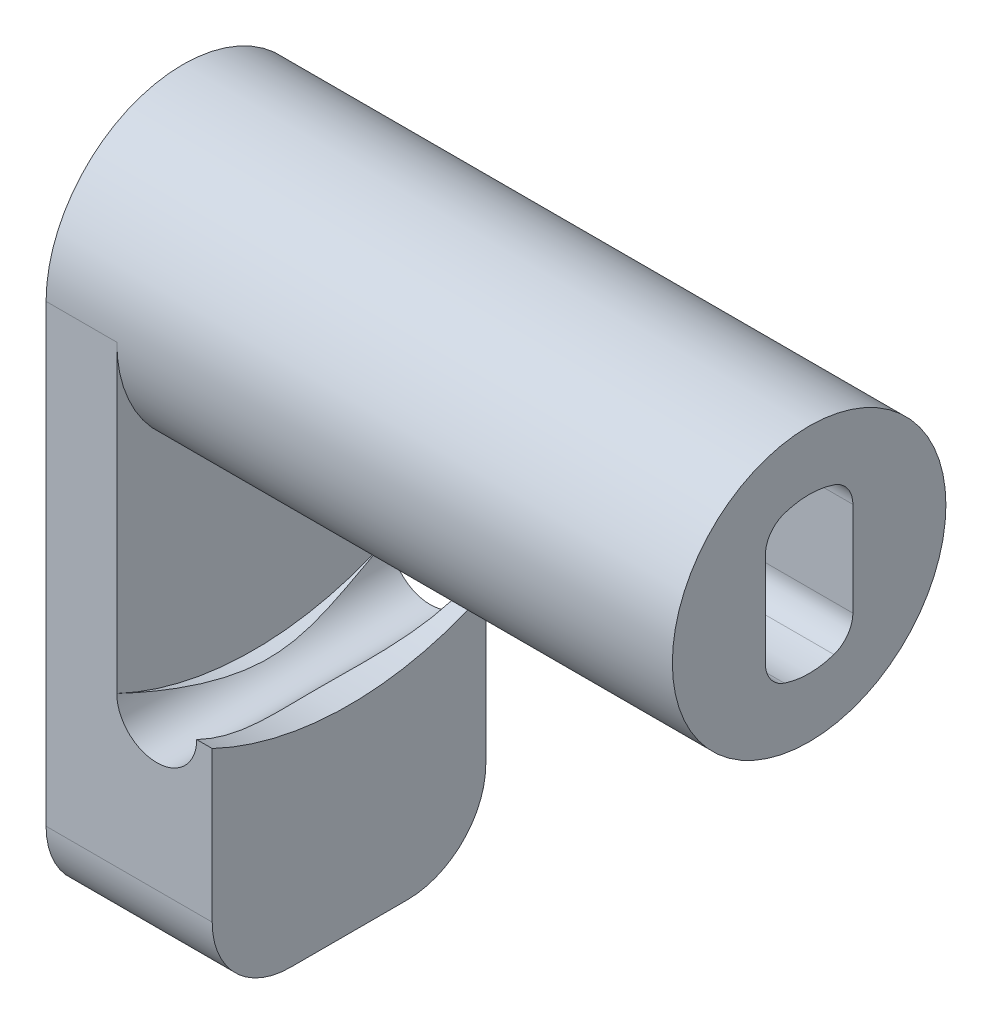
SolidWorks part; units mm, degrees
material "ABS"
ref_plane "Front Plane" through (0, 0, 0) normal (1, 0, 0) x (0, 1, 0)
ref_plane "Top Plane" through (0, 0, 0) normal (0, 0, 1) x (0, 1, 0)
ref_plane "Right Plane" through (0, 0, 0) normal (0, 1, 0) x (-1, 0, 0)
sketch "Sketch1" plane through (0, 0, 0) normal (1, 0, 0) x (0, 1, 0)
  circle A2 centre (0, 0) radius 8.7376
  dimension "D3" = 17.4752
extrude "Boss-Extrude1" add sketch "Sketch1" along normal blind 40.005 contours A2 region at (0, 0, 0)
sketch "Sketch10" plane through (0, 0, 0) normal (-1, 0, 0) x (0, -1, 0)
  line L0 (0, 8.7376) -> (34.036, 8.7376)
  line L2 (34.036, 8.7376) -> (34.036, -8.7376)
  line L3 (34.036, -8.7376) -> (0, -8.7376)
  circle A0 centre (0, 0) radius 8.7376 construction
  arc A2 (0, 8.7376) -> (0, -8.7376) centre (0, 0) cw
  dimension "D1" = 34.036
extrude "Boss-Extrude3" add sketch "Sketch10" against normal blind 4.516 contours L0 A2 L3 L2 region at (0, -20.3793, 0)
fillet "Fillet2" radius 5 2 edges at (2.258, -34.036, 8.7376) (2.258, -34.036, -8.7376)
sketch "Sketch14" [suppressed] plane through (0, 0, 0) normal (-1, 0, 0) x (0, 0, 1)
  line L0 (0.5115, -3.4237) -> (0.3944, -4.0089)
  line L1 (0, 0) -> (0, -4.064) construction
  line L2 (0, 0) -> (0.5606, -3.4335) construction
  line L3 (0.6039, -3.4087) -> (0.9011, -3.9262)
  line L4 (-0.6903, -3.3922) -> (-1.0005, -3.9021)
  line L5 (-0.5983, -3.4096) -> (-0.4961, -3.9976)
  line L6 (-1.8089, -2.9515) -> (-2.2748, -3.3245)
  line L7 (-1.7284, -2.9994) -> (-1.8334, -3.5869)
  line L8 (-2.7093, -2.1549) -> (-3.2746, -2.346)
  line L9 (-2.65, -2.2273) -> (-2.9496, -2.7435)
  line L10 (-3.2829, -1.0983) -> (-3.8795, -1.0846)
  line L11 (-3.252, -1.1867) -> (-3.7101, -1.5692)
  line L12 (-3.4605, 0.0907) -> (-4.0165, 0.3077)
  line L13 (-3.4617, -0.0029) -> (-4.023, -0.2057)
  line L14 (-3.2208, 1.2689) -> (-3.669, 1.6629)
  line L15 (-3.2539, 1.1813) -> (-3.8507, 1.1827)
  line L16 (-2.5926, 2.2939) -> (-2.879, 2.8175)
  line L17 (-2.6537, 2.223) -> (-3.214, 2.4284)
  line L18 (-1.6517, 3.0423) -> (-1.7417, 3.6323)
  line L19 (-1.7333, 2.9965) -> (-2.1896, 3.3812)
  line L20 (-0.5115, 3.4237) -> (-0.3944, 4.0089)
  line L21 (-0.6039, 3.4087) -> (-0.9011, 3.9262)
  line L22 (0.6903, 3.3922) -> (1.0005, 3.9021)
  line L23 (0.5983, 3.4096) -> (0.4961, 3.9976)
  line L24 (1.8089, 2.9515) -> (2.2748, 3.3245)
  line L25 (1.7284, 2.9994) -> (1.8334, 3.5869)
  line L26 (2.7093, 2.1549) -> (3.2746, 2.346)
  line L27 (2.65, 2.2273) -> (2.9496, 2.7435)
  line L28 (3.2829, 1.0983) -> (3.8795, 1.0846)
  line L29 (3.252, 1.1867) -> (3.7101, 1.5692)
  line L30 (3.4605, -0.0907) -> (4.0165, -0.3077)
  line L31 (3.4617, 0.0029) -> (4.023, 0.2057)
  line L32 (3.2208, -1.2689) -> (3.669, -1.6629)
  line L33 (3.2539, -1.1813) -> (3.8507, -1.1827)
  line L34 (2.5926, -2.2939) -> (2.879, -2.8175)
  line L35 (2.6537, -2.223) -> (3.214, -2.4284)
  line L36 (1.6517, -3.0423) -> (1.7417, -3.6323)
  line L37 (1.7333, -2.9965) -> (2.1896, -3.3812)
  line L38 (-0.1032, -4.0627) -> (0, -4.064)
  line L39 (-1.4865, -3.7824) -> (-1.39, -3.8189)
  line L40 (-2.6905, -3.0459) -> (-2.6123, -3.1132)
  line L41 (-3.5195, -2.032) -> (-3.57, -1.942)
  line L42 (-4.0023, -0.7057) -> (-4.0189, -0.6039)
  line L43 (-4.0023, 0.7057) -> (-3.9831, 0.8071)
  line L44 (-3.5195, 2.032) -> (-3.4668, 2.1207)
  line L45 (-2.6123, 3.1132) -> (-2.5324, 3.1785)
  line L46 (-1.39, 3.8189) -> (-1.2926, 3.853)
  line L47 (0, 4.064) -> (0.1032, 4.0627)
  line L48 (1.39, 3.8189) -> (1.4865, 3.7824)
  line L49 (2.6123, 3.1132) -> (2.6905, 3.0459)
  line L50 (3.5195, 2.032) -> (3.57, 1.942)
  line L51 (4.0023, 0.7057) -> (4.0189, 0.6039)
  line L52 (4.0023, -0.7057) -> (3.9831, -0.8071)
  line L53 (3.5195, -2.032) -> (3.4668, -2.1207)
  line L54 (2.6123, -3.1132) -> (2.5324, -3.1785)
  line L55 (1.39, -3.8189) -> (1.2926, -3.853)
  arc A0 (0.3497, -4.0489) -> (0, -4.064) centre (0, 0) cw
  arc A1 (0.3497, -4.0489) -> (0.3944, -4.0089) centre (0.3454, -3.9991) ccw
  arc A2 (0.5115, -3.4237) -> (0.6039, -3.4087) centre (0.5606, -3.4335) cw
  arc A3 (0.4203, -4.0631) -> (0.3944, -4.0089) centre (0.4434, -4.0187) cw
  arc A4 (0.4203, -4.0631) -> (0.7372, -4.2116) centre (2.3016, -0.4608) ccw
  arc A6 (0.9562, -3.9499) -> (0.9011, -3.9262) centre (0.9445, -3.9013) cw
  arc A7 (0.9562, -3.9499) -> (1.2926, -3.853) centre (0, 0) ccw
  arc A8 (-1.0562, -3.9243) -> (-1.39, -3.8189) centre (0, 0) cw
  arc A9 (-1.0562, -3.9243) -> (-1.0005, -3.9021) centre (-1.0432, -3.8761) ccw
  arc A10 (-0.6903, -3.3922) -> (-0.5983, -3.4096) centre (-0.6476, -3.4182) cw
  arc A11 (-0.4524, -4.0387) -> (-0.4961, -3.9976) centre (-0.4468, -3.9891) cw
  arc A12 (-0.4524, -4.0387) -> (-0.1032, -4.0627) centre (0, 0) ccw
  arc A13 (-2.3347, -3.3264) -> (-2.6123, -3.1132) centre (0, 0) cw
  arc A14 (-2.3347, -3.3264) -> (-2.2748, -3.3245) centre (-2.306, -3.2855) ccw
  arc A15 (-1.8089, -2.9515) -> (-1.7284, -2.9994) centre (-1.7776, -2.9906) cw
  arc A16 (-1.8064, -3.6405) -> (-1.8334, -3.5869) centre (-1.7842, -3.5957) cw
  arc A17 (-1.8064, -3.6405) -> (-1.4865, -3.7824) centre (0, 0) ccw
  arc A18 (-3.3316, -2.3273) -> (-3.5195, -2.032) centre (0, 0) cw
  arc A19 (-3.3316, -2.3273) -> (-3.2746, -2.346) centre (-3.2906, -2.2987) ccw
  arc A20 (-2.7093, -2.1549) -> (-2.65, -2.2273) centre (-2.6933, -2.2022) cw
  arc A21 (-2.9426, -2.8031) -> (-2.9496, -2.7435) centre (-2.9064, -2.7686) cw
  arc A22 (-2.9426, -2.8031) -> (-2.6905, -3.0459) centre (0, 0) ccw
  arc A23 (-3.9267, -1.0475) -> (-4.0023, -0.7057) centre (0, 0) cw
  arc A24 (-3.9267, -1.0475) -> (-3.8795, -1.0846) centre (-3.8784, -1.0346) ccw
  arc A25 (-3.2829, -1.0983) -> (-3.252, -1.1867) centre (-3.284, -1.1483) cw
  arc A26 (-3.7238, -1.6276) -> (-3.7101, -1.5692) centre (-3.678, -1.6076) cw
  arc A27 (-3.7238, -1.6276) -> (-3.57, -1.942) centre (0, 0) ccw
  arc A28 (-4.0481, 0.3587) -> (-4.0023, 0.7057) centre (0, 0) cw
  arc A29 (-4.0481, 0.3587) -> (-4.0165, 0.3077) centre (-3.9983, 0.3543) ccw
  arc A30 (-3.4605, 0.0907) -> (-3.4617, -0.0029) centre (-3.4787, 0.0442) cw
  arc A31 (-4.0559, -0.2558) -> (-4.023, -0.2057) centre (-4.006, -0.2527) cw
  arc A32 (-4.0559, -0.2558) -> (-4.0189, -0.6039) centre (0, 0) ccw
  arc A33 (-3.6813, 1.7216) -> (-3.5195, 2.032) centre (0, 0) cw
  arc A34 (-3.6813, 1.7216) -> (-3.669, 1.6629) centre (-3.636, 1.7005) ccw
  arc A35 (-3.2208, 1.2689) -> (-3.2539, 1.1813) centre (-3.2538, 1.2313) cw
  arc A36 (-3.8988, 1.1468) -> (-3.8507, 1.1827) centre (-3.8509, 1.1327) cw
  arc A37 (-3.8988, 1.1468) -> (-3.9831, 0.8071) centre (0, 0) ccw
  arc A38 (-2.8705, 2.8769) -> (-2.6123, 3.1132) centre (0, 0) cw
  arc A39 (-2.8705, 2.8769) -> (-2.879, 2.8175) centre (-2.8352, 2.8415) ccw
  arc A40 (-2.5926, 2.2939) -> (-2.6537, 2.223) centre (-2.6365, 2.2699) cw
  arc A41 (-3.2715, 2.4111) -> (-3.214, 2.4284) centre (-3.2312, 2.3815) cw
  arc A42 (-3.2715, 2.4111) -> (-3.4668, 2.1207) centre (0, 0) ccw
  arc A43 (-1.7134, 3.6852) -> (-1.39, 3.8189) centre (0, 0) cw
  arc A44 (-1.7134, 3.6852) -> (-1.7417, 3.6323) centre (-1.6923, 3.6398) ccw
  arc A45 (-1.6517, 3.0423) -> (-1.7333, 2.9965) centre (-1.7011, 3.0348) cw
  arc A46 (-2.2495, 3.3846) -> (-2.1896, 3.3812) centre (-2.2218, 3.343) cw
  arc A47 (-2.2495, 3.3846) -> (-2.5324, 3.1785) centre (0, 0) ccw
  arc A48 (-0.3497, 4.0489) -> (0, 4.064) centre (0, 0) cw
  arc A49 (-0.3497, 4.0489) -> (-0.3944, 4.0089) centre (-0.3454, 3.9991) ccw
  arc A50 (-0.5115, 3.4237) -> (-0.6039, 3.4087) centre (-0.5606, 3.4335) cw
  arc A51 (-0.9562, 3.9499) -> (-0.9011, 3.9262) centre (-0.9445, 3.9013) cw
  arc A52 (-0.9562, 3.9499) -> (-1.2926, 3.853) centre (0, 0) ccw
  arc A53 (1.0562, 3.9243) -> (1.39, 3.8189) centre (0, 0) cw
  arc A54 (1.0562, 3.9243) -> (1.0005, 3.9021) centre (1.0432, 3.8761) ccw
  arc A55 (0.6903, 3.3922) -> (0.5983, 3.4096) centre (0.6476, 3.4182) cw
  arc A56 (0.4524, 4.0387) -> (0.4961, 3.9976) centre (0.4468, 3.9891) cw
  arc A57 (0.4524, 4.0387) -> (0.1032, 4.0627) centre (0, 0) ccw
  arc A58 (2.3347, 3.3264) -> (2.6123, 3.1132) centre (0, 0) cw
  arc A59 (2.3347, 3.3264) -> (2.2748, 3.3245) centre (2.306, 3.2855) ccw
  arc A60 (1.8089, 2.9515) -> (1.7284, 2.9994) centre (1.7776, 2.9906) cw
  arc A61 (1.8064, 3.6405) -> (1.8334, 3.5869) centre (1.7842, 3.5957) cw
  arc A62 (1.8064, 3.6405) -> (1.4865, 3.7824) centre (0, 0) ccw
  arc A63 (3.3316, 2.3273) -> (3.5195, 2.032) centre (0, 0) cw
  arc A64 (3.3316, 2.3273) -> (3.2746, 2.346) centre (3.2906, 2.2987) ccw
  arc A65 (2.7093, 2.1549) -> (2.65, 2.2273) centre (2.6933, 2.2022) cw
  arc A66 (2.9426, 2.8031) -> (2.9496, 2.7435) centre (2.9064, 2.7686) cw
  arc A67 (2.9426, 2.8031) -> (2.6905, 3.0459) centre (0, 0) ccw
  arc A68 (3.9267, 1.0475) -> (4.0023, 0.7057) centre (0, 0) cw
  arc A69 (3.9267, 1.0475) -> (3.8795, 1.0846) centre (3.8784, 1.0346) ccw
  arc A70 (3.2829, 1.0983) -> (3.252, 1.1867) centre (3.284, 1.1483) cw
  arc A71 (3.7238, 1.6276) -> (3.7101, 1.5692) centre (3.678, 1.6076) cw
  arc A72 (3.7238, 1.6276) -> (3.57, 1.942) centre (0, 0) ccw
  arc A73 (4.0481, -0.3587) -> (4.0023, -0.7057) centre (0, 0) cw
  arc A74 (4.0481, -0.3587) -> (4.0165, -0.3077) centre (3.9983, -0.3543) ccw
  arc A75 (3.4605, -0.0907) -> (3.4617, 0.0029) centre (3.4787, -0.0442) cw
  arc A76 (4.0559, 0.2558) -> (4.023, 0.2057) centre (4.006, 0.2527) cw
  arc A77 (4.0559, 0.2558) -> (4.0189, 0.6039) centre (0, 0) ccw
  arc A78 (3.6813, -1.7216) -> (3.5195, -2.032) centre (0, 0) cw
  arc A79 (3.6813, -1.7216) -> (3.669, -1.6629) centre (3.636, -1.7005) ccw
  arc A80 (3.2208, -1.2689) -> (3.2539, -1.1813) centre (3.2538, -1.2313) cw
  arc A81 (3.8988, -1.1468) -> (3.8507, -1.1827) centre (3.8509, -1.1327) cw
  arc A82 (3.8988, -1.1468) -> (3.9831, -0.8071) centre (0, 0) ccw
  arc A83 (2.8705, -2.8769) -> (2.6123, -3.1132) centre (0, 0) cw
  arc A84 (2.8705, -2.8769) -> (2.879, -2.8175) centre (2.8352, -2.8415) ccw
  arc A85 (2.5926, -2.2939) -> (2.6537, -2.223) centre (2.6365, -2.2699) cw
  arc A86 (3.2715, -2.4111) -> (3.214, -2.4284) centre (3.2312, -2.3815) cw
  arc A87 (3.2715, -2.4111) -> (3.4668, -2.1207) centre (0, 0) ccw
  arc A88 (1.7134, -3.6852) -> (1.39, -3.8189) centre (0, 0) cw
  arc A89 (1.7134, -3.6852) -> (1.7417, -3.6323) centre (1.6923, -3.6398) ccw
  arc A90 (1.6517, -3.0423) -> (1.7333, -2.9965) centre (1.7011, -3.0348) cw
  arc A91 (2.2495, -3.3846) -> (2.1896, -3.3812) centre (2.2218, -3.343) cw
  arc A92 (2.2495, -3.3846) -> (2.5324, -3.1785) centre (0, 0) ccw
  point P207 (0, 0)
  dimension "D1" = 4.064
  dimension "D2" = 0.05
  dimension "D3" = 0.05
  dimension "D4" = 0.04
  dimension "D5" = 18
  dimension "D6" = 0.5968
  dimension "D8" = 0.35
sketch "Sketch15" plane through (4.516, 0, 0) normal (1, 0, 0) x (0, 1, 0)
  line L1 (-29.036, 8.7376) -> (-18.796, 8.7376)
  line L2 (-18.796, 8.7376) -> (-18.796, -8.7376)
  line L3 (0, 8.7376) -> (-29.036, 8.7376) construction
  line L4 (-29.036, -8.7376) -> (-18.796, -8.7376)
  line L5 (-34.036, 3.7376) -> (-34.036, -3.7376) construction
  line L6 (-34.036, 3.7376) -> (-34.036, -3.7376)
  line L8 (-29.036, -8.7376) -> (0, -8.7376) construction
  line L13 (0, 8.7376) -> (-29.036, 8.7376)
  line L14 (-34.036, 3.7376) -> (-34.036, -3.7376)
  line L15 (-29.036, -8.7376) -> (0, -8.7376)
  line L17 (-34.036, 3.7376) -> (-34.036, -3.7376)
  arc A0 (-29.036, 8.7376) -> (-34.036, 3.7376) centre (-29.036, 3.7376) ccw construction
  arc A1 (-34.036, -3.7376) -> (-29.036, -8.7376) centre (-29.036, -3.7376) ccw construction
  arc A2 (-29.036, 8.7376) -> (-34.036, 3.7376) centre (-29.036, 3.7376) ccw
  arc A3 (-34.036, -3.7376) -> (-29.036, -8.7376) centre (-29.036, -3.7376) ccw
  arc A7 (-29.036, 8.7376) -> (-34.036, 3.7376) centre (-29.036, 3.7376) ccw
  arc A8 (-34.036, -3.7376) -> (-29.036, -8.7376) centre (-29.036, -3.7376) ccw
  arc A9 (0, 8.7376) -> (0, -8.7376) centre (0, 0) ccw
  arc A10 (-29.036, 8.7376) -> (-34.036, 3.7376) centre (-29.036, 3.7376) ccw
  arc A11 (-34.036, -3.7376) -> (-29.036, -8.7376) centre (-29.036, -3.7376) ccw
  arc A12 (0, 8.7376) -> (0, -8.7376) centre (0, 0) ccw
  line M2 (0, 8.7376) -> (-29.036, 8.7376)
  arc M3 (-29.036, 8.7376) -> (-34.036, 3.7376) centre (-29.036, 3.7376) ccw
  line M4 (-34.036, 3.7376) -> (-34.036, -3.7376)
  arc M5 (-34.036, -3.7376) -> (-29.036, -8.7376) centre (-29.036, -3.7376) ccw
  dimension "D1" = 15.24
  dimension "D2" = 0
extrude "Boss-Extrude4" add sketch "Sketch15" along normal blind 6.096 contours M2 M3 M4 M5 region at (4.516, -26.143, 0)
sketch "Sketch21" plane through (10.612, 0, 0) normal (1, 0, 0) x (0, 1, 0)
  line L2 (-18.796, -8.7376) -> (-18.796, 8.7376)
  line L4 (-29.036, 8.7376) -> (-18.796, 8.7376) construction
  line L5 (-19.431, -8.7376) -> (-18.796, -8.7376)
  line L6 (-18.796, 8.7376) -> (-18.796, -8.7376) construction
  line L8 (-18.796, -8.7376) -> (0, -8.7376) construction
  line L14 (-18.796, -8.7376) -> (-18.796, 8.7376) construction
  line L20 (-18.796, 8.7376) -> (-29.036, 8.7376)
  arc A2 (-19.431, -8.7376) -> (-19.431, 8.7376) centre (-1.0855, 0) cw
  dimension "D4" = 20.32
  dimension "D2" = 0.635
  dimension "D3" = 0.635
extrude "Cut-Extrude8" cut sketch "Sketch21" against normal up to surface (6.096 mm away) contours A2 L2 region at (10.612, -19.8652, 0) up to face at (4.516, -11.5824, 0)
sketch "Sketch22" plane through (40.005, 0, 0) normal (1, 0, 0) x (0, 1, 0)
  line L7 (-4.0897, -2.794) -> (4.0897, 2.794) construction
  line L8 (-4.0897, 2.794) -> (4.0897, -2.794) construction
  line L11 (-4.0897, -2.794) -> (4.0897, -2.794)
  line L13 (-4.0897, 2.794) -> (4.0897, 2.794)
  line L15 (-4.0897, -2.794) -> (4.0897, 2.794) construction
  line L16 (-4.0897, 2.794) -> (4.0897, -2.794) construction
  arc A3 (-4.0897, 2.794) -> (-4.0897, -2.794) centre (0, 0) ccw
  arc A4 (4.0897, -2.794) -> (4.0897, 2.794) centre (0, 0) ccw
  dimension "D2" = 9.906
  dimension "D3" = 5.588
extrude "Cut-Extrude10" cut sketch "Sketch22" against normal blind 12.192
fillet "Fillet11" radius 1.778 4 edges at (33.909, 4.0897, -2.794) (33.909, 4.0897, 2.794) (33.909, -4.0897, -2.794) (33.909, -4.0897, 2.794)
sketch "Sketch25" plane through (0, 0, -8.7376) normal (0, 0, -1) x (1, 0, 0)
  line L3 (4.516, 19.431) -> (4.516, 0) construction
  line L4 (4.516, 19.431) -> (10.612, 19.431) construction
  circle A0 centre (7.0687, 19.431) radius 2.5527
  dimension "D1" = 5.1054
extrude "Cut-Extrude14" cut sketch "Sketch25" against normal through all
sketch "Sketch26" plane through (0, 0, 0) normal (-1, 0, 0) x (0, -1, 0)
  line L1 (3.6846, 1.7145) -> (7.1771, 1.7145)
  line L2 (3.6846, 1.7145) -> (3.6846, -1.7145) construction
  line L3 (3.6846, -1.7145) -> (7.1771, -1.7145)
  line L4 (7.1771, 1.7145) -> (7.1771, -1.7145)
  arc A0 (3.6846, 1.7145) -> (3.6846, -1.7145) centre (0, 0) ccw
  dimension "D1" = 8.128
  dimension "D2" = 3.429
  dimension "D3" = 3.4925
extrude "Cut-Extrude15" cut sketch "Sketch26" against normal blind 21.59
fillet "Fillet12" radius 1.5875 4 edges at (10.795, -3.6846, 1.7145) (10.795, -7.1771, 1.7145) (10.795, -3.6846, -1.7145) (10.795, -7.1771, -1.7145)
